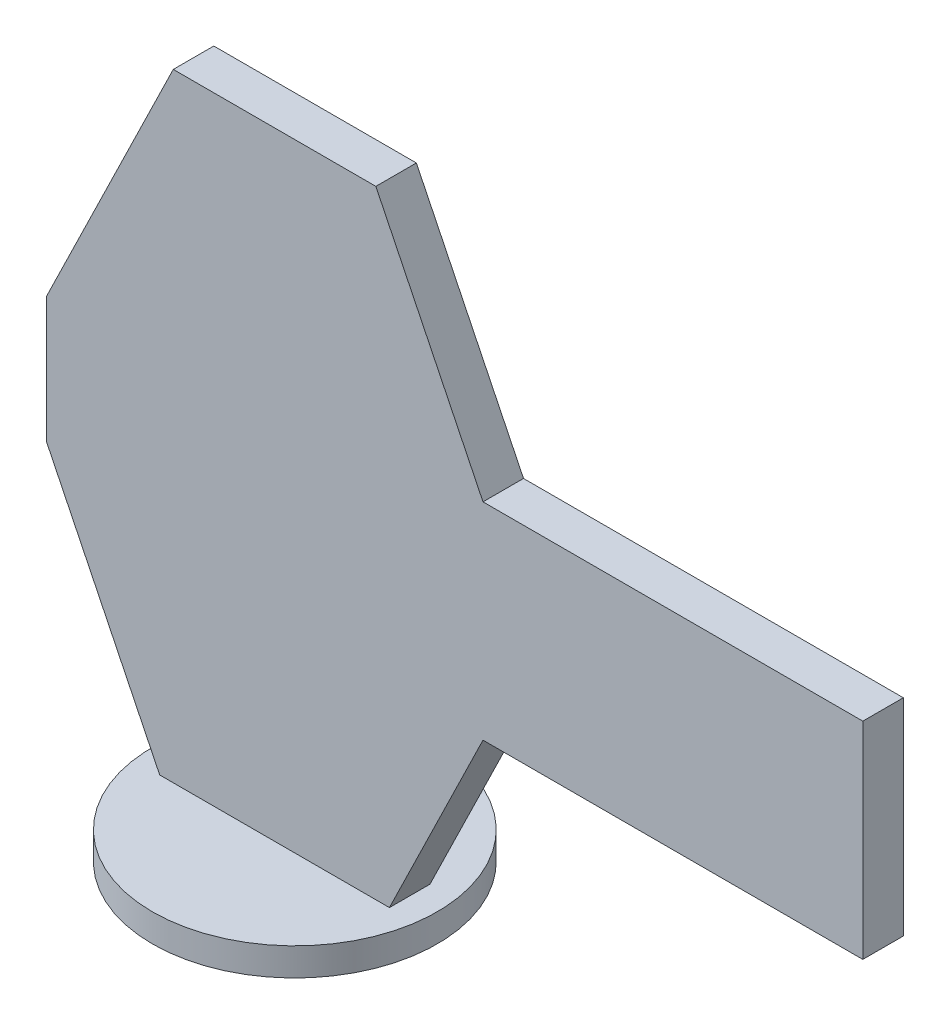
SolidWorks part; units mm, degrees
ref_plane "Front Plane" through (0, 0, 0) normal (0, 0, 1) x (1, 0, 0)
ref_plane "Top Plane" through (0, 0, 0) normal (0, 1, 0) x (1, 0, 0)
ref_plane "Right Plane" through (0, 0, 0) normal (1, 0, 0) x (0, 0, -1)
sketch "Sketch1" plane through (0, 0, 0) normal (0, 1, 0) x (1, 0, 0)
  circle A0 centre (0, 0) radius 11.25
  dimension "D1" = 22.5
extrude "Boss-Extrude1" add sketch "Sketch1" along normal blind 2.2
sketch "Sketch2" plane through (0, 0, 0) normal (0, 0, 1) x (1, 0, 0)
  line L0 (0, 0) -> (0, 61.0724) construction
  line L5 (-8, 51) -> (8, 51)
  line L6 (-11.25, 0) -> (11.25, 0) construction
  line L9 (-24.3266, 20.5) -> (26.688, 20.5) construction
  line L10 (-24.3266, 30.5) -> (26.688, 30.5) construction
  line L11 (-18, 30.5) -> (-18, 20.5)
  line L12 (18, 30.5) -> (18, 20.5)
  line L13 (-8, 51) -> (-18, 30.5)
  line L15 (8, 51) -> (18, 30.5)
  line L16 (18, 20.5) -> (8, 0)
  line L17 (8, 0) -> (-8, 0)
  line L22 (-8, 0) -> (-18, 20.5)
  point P17 (18, 25.5)
  dimension "D1" = 16
  dimension "D2" = 8
  dimension "D3" = 51
  dimension "D4" = 20.5
  dimension "D5" = 10
  dimension "D6" = 18
  dimension "D7" = 18
  dimension "D8" = 8
  dimension "D9" = 8
extrude "Boss-Extrude2" add sketch "Sketch2" along normal blind 1.6 and the other way blind 1.6
sketch "Sketch3" plane through (0, 0, 1.6) normal (0, 0, 1) x (1, 0, 0)
  line L0 (-18, 25.5) -> (7.6577, 25.5) construction
  line L1 (13.1342, 33.65) -> (46.4634, 33.65)
  line L2 (13.1342, 33.65) -> (13.1342, 17.35)
  line L3 (13.1342, 17.35) -> (46.4634, 17.35)
  line L4 (46.4634, 33.65) -> (46.4634, 17.35)
  line L5 (-18, 30.5) -> (-18, 20.5) construction
  dimension "D1" = 16.3
  dimension "D2" = 8.15
extrude "Boss-Extrude3" add sketch "Sketch3" against normal blind 3.2
sketch "Sketch4" plane through (0, 0, 1.6) normal (0, 0, 1) x (1, 0, 0)
  line L0 (0, 0) -> (0, 44.3555) construction
  line L1 (21.0679, 33.3251) -> (19.993, 53.5478)
  line L2 (9.0984, 33.4149) -> (10.0022, 53.4268)
  arc A0 (9.0984, 33.4149) -> (21.0679, 33.3251) centre (15, 22.2825) ccw
  arc A1 (19.993, 53.5478) -> (10.0022, 53.4268) centre (15.0001, 53.2825) ccw
  dimension "D1" = 25.2
  dimension "D4" = 10
  dimension "D2" = 15
extrude "Boss-Extrude4" [suppressed] add sketch "Sketch4" along normal blind 3.2
